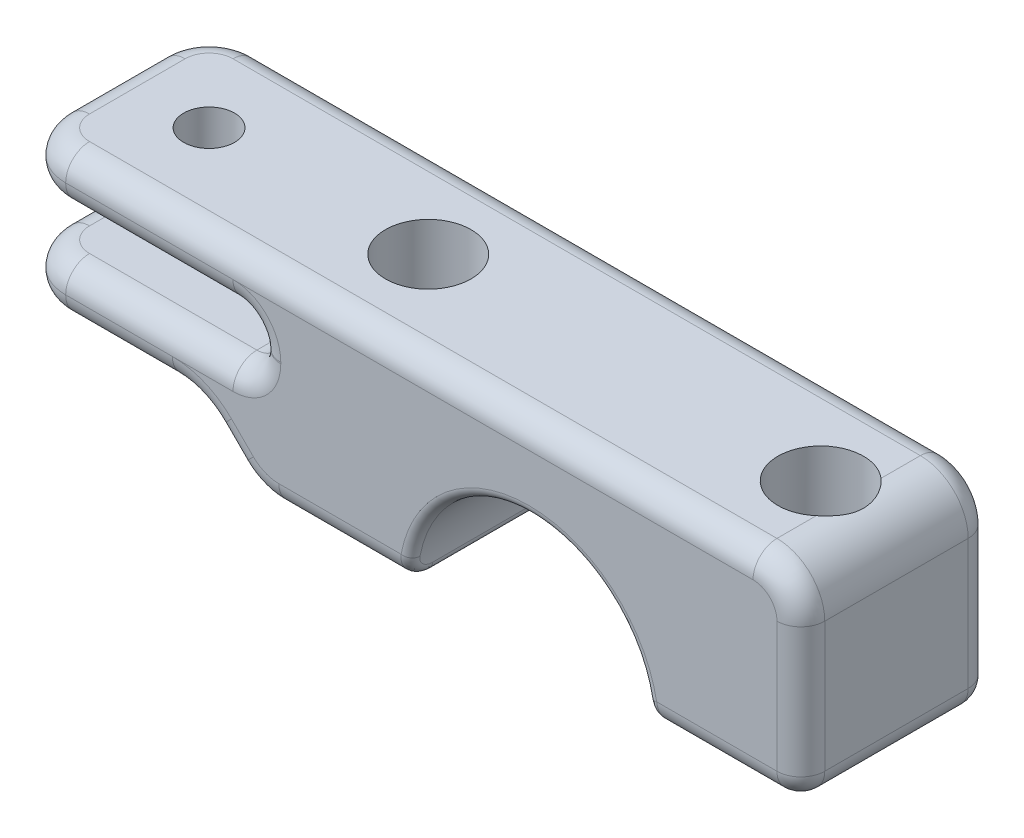
SolidWorks part; units mm, degrees
material "PLA ABS"
ref_plane "Front Plane" through (0, 0, 0) normal (0, 0, 1) x (1, 0, 0)
ref_plane "Top Plane" through (0, 0, 0) normal (0, 1, 0) x (1, 0, 0)
ref_plane "Right Plane" through (0, 0, 0) normal (1, 0, 0) x (0, 0, -1)
sketch "Sketch1" plane through (0, 0, 0) normal (0, 1, 0) x (1, 0, 0)
  line L1 (-50.8, -50.8) -> (50.8, -50.8)
  line L2 (-50.8, -50.8) -> (-50.8, 50.8)
  line L3 (-50.8, 50.8) -> (50.8, 50.8)
  line L4 (50.8, -50.8) -> (50.8, 50.8)
  line L6 (-50.8, 50.8) -> (50.8, -50.8) construction
  point P0 (0, 0)
  dimension "D1" = 101.6
  dimension "D2" = 101.6
extrude "Boss-Extrude1" add sketch "Sketch1" against normal mid plane 6.35
sketch "Sketch4" plane through (0, 0, 0) normal (0, 0, 1) x (1, 0, 0)
  line L0 (-50.8, -3.175) -> (50.8, -3.175) construction
  line L1 (-36.1315, -3.175) -> (36.1315, -3.175)
  line L2 (-36.1315, -3.175) -> (-36.1315, -19.2024)
  line L3 (-36.1315, -19.2024) -> (-16.002, -19.2024)
  line L4 (36.1315, -3.175) -> (36.1315, -19.2024)
  line L5 (0, -3.175) -> (0, 0) construction
  line L6 (16.002, -19.2024) -> (36.1315, -19.2024)
  line L7 (-16.002, -19.2024) -> (16.002, -19.2024) construction
  line L8 (-26.0667, -19.2024) -> (-26.0667, -3.175) construction
  line L9 (-29.3941, -3.175) -> (-22.7394, -3.175) construction
  line L10 (-29.3941, -19.2024) -> (-29.3941, -3.175) construction
  line L11 (22.7394, -19.2024) -> (22.7394, -3.175) construction
  line L12 (-22.7394, -19.2024) -> (-22.7394, -3.175) construction
  line L13 (26.0667, -19.2024) -> (26.0667, -3.175) construction
  line L14 (29.3941, -19.2024) -> (29.3941, -3.175) construction
  arc A0 (16.002, -19.2024) -> (-16.002, -19.2024) centre (0, -19.2024) ccw
  dimension "D1" = 32.004
  dimension "D2" = 0.0254
  dimension "D3" = 72.263
  dimension "D4" = 6.6548
extrude "Boss-Extrude3" add sketch "Sketch4" along normal mid plane 25.4
sketch "Sketch6" plane through (0, -19.2024, 0) normal (0, -1, 0) x (1, 0, 0)
  line L0 (-36.1315, 12.7) -> (-16.002, 12.7) construction
  line L1 (-26.0667, 12.7) -> (-26.0667, -12.7) construction
  line L3 (36.1315, 12.7) -> (-36.1315, 12.7) construction
  line L4 (16.002, 12.7) -> (36.1315, 12.7) construction
  line L5 (36.1315, 12.7) -> (16.002, 12.7) construction
  line L6 (-22.225, 22.225) -> (0, 22.225) construction
  line L7 (26.0667, 12.7) -> (26.0667, -12.7) construction
  line L8 (16.002, -12.7) -> (36.1315, -12.7) construction
  line L9 (0, 22.225) -> (22.225, 22.225) construction
  line L10 (-22.225, 22.225) -> (-22.225, -22.225) construction
  line L11 (36.1315, 0) -> (0, 0) construction
  line L13 (0, 0) -> (0, 50.8) construction
  line L14 (-50.8, 50.8) -> (50.8, 50.8) construction
  line L15 (-22.225, -22.225) -> (22.225, -22.225) construction
  line L16 (22.225, 22.225) -> (22.225, 0) construction
  line L17 (22.225, 0) -> (22.225, -22.225) construction
  line L19 (36.1315, 12.7) -> (36.1315, -12.7) construction
  line L24 (-11.176, 50.8) -> (-11.176, -50.8) construction
  line L25 (-50.8, 50.8) -> (50.8, 50.8) construction
  line L26 (50.8, -50.8) -> (-50.8, -50.8) construction
  line L27 (-11.176, 25.4) -> (0, 25.4) construction
  line L28 (11.176, -50.8) -> (11.176, 50.8) construction
  line L29 (0, 25.4) -> (11.176, 25.4) construction
  circle A0 centre (-26.0667, 0) radius 3.3274
  circle A1 centre (26.0667, 0) radius 3.3274
  circle A8 centre (-22.225, 22.225) radius 3.3274
  circle A9 centre (22.225, 22.225) radius 3.3274
  circle A12 centre (22.225, -22.225) radius 3.3274
  circle A13 centre (-22.225, -22.225) radius 3.3274
  dimension "D1" = 44.45
  dimension "D3" = 44.45
  dimension "D4" = 6.6548
  dimension "D2" = 22.352
extrude "Cut-Extrude1" cut sketch "Sketch6" against normal through all
sketch "Sketch7" plane through (0, 3.175, 0) normal (0, 1, 0) x (1, 0, 0)
  line L1 (-19.5043, 0) -> (-22.7855, 5.6833) construction
  line L2 (-22.7855, 5.6833) -> (-29.348, 5.6833) construction
  line L3 (-29.348, 5.6833) -> (-32.6292, 0) construction
  line L4 (-32.6292, 0) -> (-29.348, -5.6833) construction
  line L5 (-29.348, -5.6833) -> (-22.7855, -5.6833) construction
  line L6 (-22.7855, -5.6833) -> (-19.5043, 0) construction
  line L7 (32.6292, 0) -> (29.348, 5.6833) construction
  line L8 (29.348, 5.6833) -> (22.7855, 5.6833) construction
  line L9 (22.7855, 5.6833) -> (19.5043, 0) construction
  line L10 (19.5043, 0) -> (22.7855, -5.6833) construction
  line L11 (22.7855, -5.6833) -> (29.348, -5.6833) construction
  line L12 (29.348, -5.6833) -> (32.6292, 0) construction
  circle A0 centre (-26.0667, 0) radius 5.6833
  circle A1 centre (26.0667, 0) radius 5.6833
  dimension "D1" = 11.3665
extrude "Cut-Extrude2" cut sketch "Sketch7" against normal blind 4.0704
sketch "Sketch9" plane through (0, -3.175, 0) normal (0, -1, 0) x (1, 0, 0)
  line L1 (-25.9715, -36.1315) -> (25.9715, -36.1315)
  line L2 (-36.1315, -25.9715) -> (-36.1315, 25.9715)
  line L3 (-25.9715, 36.1315) -> (25.9715, 36.1315)
  line L4 (36.1315, -25.9715) -> (36.1315, 25.9715)
  line L5 (-36.1315, -36.1315) -> (36.1315, 36.1315) construction
  line L6 (-36.1315, 36.1315) -> (36.1315, -36.1315) construction
  line L8 (-50.8, -50.8) -> (50.8, -50.8)
  line L9 (-50.8, -50.8) -> (-50.8, 50.8)
  line L10 (-50.8, 50.8) -> (50.8, 50.8)
  line L11 (50.8, -50.8) -> (50.8, 50.8)
  line L12 (-50.8, -50.8) -> (50.8, 50.8) construction
  line L13 (-50.8, 50.8) -> (50.8, -50.8) construction
  arc A0 (-25.9715, -36.1315) -> (-36.1315, -25.9715) centre (-25.9715, -25.9715) cw
  arc A1 (25.9715, -36.1315) -> (36.1315, -25.9715) centre (25.9715, -25.9715) ccw
  arc A2 (25.9715, 36.1315) -> (36.1315, 25.9715) centre (25.9715, 25.9715) cw
  arc A3 (-36.1315, 25.9715) -> (-25.9715, 36.1315) centre (-25.9715, 25.9715) cw
  circle A5 centre (-22.225, -22.225) radius 3.3274 construction
  point P0 (0, 0)
  point P20 (0, 0)
  dimension "D1" = 10.16
  dimension "D2" = 8.189
  dimension "D3" = 72.263
extrude "Cut-Extrude3" cut sketch "Sketch9" against normal through all
sketch "Sketch10" plane through (0, -3.175, 0) normal (0, -1, 0) x (1, 0, 0)
  line L4 (-36.1315, 25.9715) -> (-36.1315, 12.7)
  line L5 (-36.1315, 12.7) -> (36.1315, 12.7)
  line L6 (36.1315, 12.7) -> (36.1315, 25.9715)
  line L7 (25.9715, 36.1315) -> (-25.9715, 36.1315)
  line L8 (-36.1315, 25.9715) -> (-36.1315, 12.7)
  line L9 (-36.1315, 12.7) -> (36.1315, 12.7)
  line L10 (36.1315, 12.7) -> (36.1315, 25.9715)
  line L11 (25.9715, 36.1315) -> (-25.9715, 36.1315)
  line L12 (36.1315, -12.7) -> (-36.1315, -12.7)
  line L13 (-36.1315, -12.7) -> (-36.1315, -25.9715)
  line L14 (-25.9715, -36.1315) -> (25.9715, -36.1315)
  line L15 (36.1315, -25.9715) -> (36.1315, -12.7)
  line L16 (36.1315, -12.7) -> (-36.1315, -12.7)
  line L17 (-36.1315, -12.7) -> (-36.1315, -25.9715)
  line L18 (-25.9715, -36.1315) -> (25.9715, -36.1315)
  line L19 (36.1315, -25.9715) -> (36.1315, -12.7)
  arc A2 (-25.9715, 36.1315) -> (-36.1315, 25.9715) centre (-25.9715, 25.9715) ccw
  arc A3 (36.1315, 25.9715) -> (25.9715, 36.1315) centre (25.9715, 25.9715) ccw
  arc A4 (-25.9715, 36.1315) -> (-36.1315, 25.9715) centre (-25.9715, 25.9715) ccw
  arc A5 (36.1315, 25.9715) -> (25.9715, 36.1315) centre (25.9715, 25.9715) ccw
  arc A6 (-36.1315, -25.9715) -> (-25.9715, -36.1315) centre (-25.9715, -25.9715) ccw
  arc A7 (25.9715, -36.1315) -> (36.1315, -25.9715) centre (25.9715, -25.9715) ccw
  arc A8 (-36.1315, -25.9715) -> (-25.9715, -36.1315) centre (-25.9715, -25.9715) ccw
  arc A9 (25.9715, -36.1315) -> (36.1315, -25.9715) centre (25.9715, -25.9715) ccw
  dimension "D1" = 0
  dimension "D2" = 0
extrude "Cut-Extrude4" cut sketch "Sketch10" against normal through all
sketch "Sketch11" plane through (0, 3.175, 0) normal (0, 1, 0) x (1, 0, 0)
  line L0 (0, 0) -> (-36.1315, 0)
  line L1 (-36.1315, -12.7) -> (-36.1315, 12.7) construction
sketch "Sketch12" plane through (0, 3.175, 0) normal (0, 1, 0) x (1, 0, 0)
  line L4 (36.1315, 12.7) -> (-36.1315, 12.7)
  line L5 (-36.1315, 12.7) -> (-36.1315, -12.7)
  line L6 (-36.1315, -12.7) -> (36.1315, -12.7)
  line L7 (36.1315, -12.7) -> (36.1315, 12.7)
  line L8 (36.1315, 12.7) -> (-36.1315, 12.7)
  line L9 (-36.1315, 12.7) -> (-36.1315, -12.7)
  line L10 (-36.1315, -12.7) -> (36.1315, -12.7)
  line L11 (36.1315, -12.7) -> (36.1315, 12.7)
  dimension "D1" = 0
extrude "Cut-Extrude5" cut sketch "Sketch12" against normal blind 1.9392
sketch "Sketch13" plane through (0, -0.8954, 0) normal (0, 1, 0) x (1, 0, 0)
  circle A0 centre (26.0667, 0) radius 5.6833 construction
  circle A1 centre (-26.0667, 0) radius 5.6833 construction
  circle A2 centre (26.0667, 0) radius 5.6833
  circle A3 centre (-26.0667, 0) radius 5.6833
extrude "Cut-Extrude6" cut sketch "Sketch13" against normal blind 1.9392
sketch "Sketch15" plane through (-36.1315, 0, 0) normal (-1, 0, 0) x (0, 0, 1)
  line L1 (-12.7, -5.292) -> (12.7, -5.292)
  line L2 (-12.7, -5.292) -> (-12.7, -11.642)
  line L3 (-12.7, -11.642) -> (12.7, -11.642)
  line L4 (12.7, -5.292) -> (12.7, -11.642)
  line L5 (-12.7, -5.292) -> (12.7, -11.642) construction
  line L6 (-12.7, -11.642) -> (12.7, -5.292) construction
  line L8 (-12.7, 1.2358) -> (12.7, 1.2358) construction
  point P0 (0, -8.467)
  dimension "D1" = 6.35
  dimension "D2" = 6.5278
extrude "Boss-Extrude4" add sketch "Sketch15" along normal blind 31.75 separate body
sketch "Sketch17" plane through (0, 1.2358, 0) normal (0, 1, 0) x (1, 0, 0)
  line L0 (36.1315, 12.7) -> (36.1315, -12.7)
  line L3 (36.1315, -12.7) -> (-67.8815, -12.7)
  line L4 (-67.8815, -12.7) -> (-67.8815, 12.7)
  line L5 (-67.8815, 12.7) -> (36.1315, 12.7)
  line L6 (36.1315, -12.7) -> (36.1315, 12.7) construction
  circle A0 centre (-26.0667, 0) radius 5.6833 construction
  circle A1 centre (-26.0667, 0) radius 5.6833
  circle A2 centre (26.0667, 0) radius 5.6833 construction
  circle A3 centre (26.0667, 0) radius 5.6833
extrude "Boss-Extrude5" add sketch "Sketch17" along normal blind 6.35
fillet "Fillet2" radius 6.35 1 edges at (36.1315, 7.5858, 0)
fillet "Fillet5" radius 6.35 4 edges at (-67.8815, -8.467, 12.7) (-67.8815, -8.467, -12.7) (-67.8815, 4.4108, -12.7) (-67.8815, 4.4108, 12.7)
sketch "Sketch16" plane through (0, -5.292, 0) normal (0, 1, 0) x (1, 0, 0)
  circle A0 centre (-55.1815, 0) radius 3.3782
  circle A1 centre (-26.0667, 0) radius 3.3274 construction
  point P4 (-26.0667, 0)
  dimension "D1" = 29.1147
  dimension "D2" = 6.7564
extrude "Cut-Extrude7" cut sketch "Sketch16" along normal through all both and the other way through all
sketch "Sketch18" plane through (0, -11.642, 0) normal (0, -1, 0) x (1, 0, 0)
  line L1 (-50.533, -4.4219) -> (-49.0277, 1.8148)
  line L2 (-49.0277, 1.8148) -> (-53.6763, 6.2367)
  line L3 (-53.6763, 6.2367) -> (-59.83, 4.4219)
  line L4 (-59.83, 4.4219) -> (-61.3353, -1.8148)
  line L5 (-61.3353, -1.8148) -> (-56.6867, -6.2367)
  line L6 (-56.6867, -6.2367) -> (-50.533, -4.4219)
  circle A0 centre (-55.1815, 0) radius 5.5563 construction
  dimension "D1" = 11.1125
chamfer "Chamfer1" distance 7.9375 angle 45 1 edges
fillet "Fillet7" radius 7.9375 2 edges at (-44.069, -11.642, 0) (-36.5086, -19.2024, 0)
fillet "Fillet8" radius 3.175 39 edges at (-67.8815, 1.2358, 0) (-67.8815, -5.292, 0) (-66.0216, 1.2358, -10.8401) (-66.0216, 1.2358, 10.8401) (-66.0216, -5.292, 10.8401) (-66.0216, -5.292, -10.8401) (36.1315, -8.9833, -12.7) (34.2716, 5.7259, -12.7) (-15.875, 7.5858, -12.7) (-66.0216, 7.5858, -10.8401) (-67.8815, 7.5858, 0) (-66.0216, 7.5858, 10.8401) (36.1315, -8.9833, 12.7) (34.2716, 5.7259, 12.7) (-24.6114, -19.2024, 12.7) (-36.2583, -18.5982, 12.7) (-40.2888, -15.4222, 12.7) (-44.3193, -12.2462, 12.7) (-24.6114, -19.2024, -12.7) (-36.2583, -18.5982, -12.7) (-40.2888, -15.4222, -12.7) (-44.3193, -12.2462, -12.7) (-66.0216, -11.642, -10.8401) (-67.8815, -11.642, 0) (-66.0216, -11.642, 10.8401) (26.0667, -19.2024, -12.7) (36.1315, -19.2024, 0) (26.0667, -19.2024, 12.7) (-15.875, 7.5858, 12.7)
fillet "Fillet9" radius 1.27 8 edges at (-15.9869, -18.5072, -11.5078) (-16.002, -19.2024, 0) (-15.9563, -17.9936, 12.0179) (0, -3.2004, 12.7) (15.9869, -18.5072, 11.5078) (16.002, -19.2024, 0) (15.9563, -17.9936, -12.0179) (0, -3.2004, -12.7)
